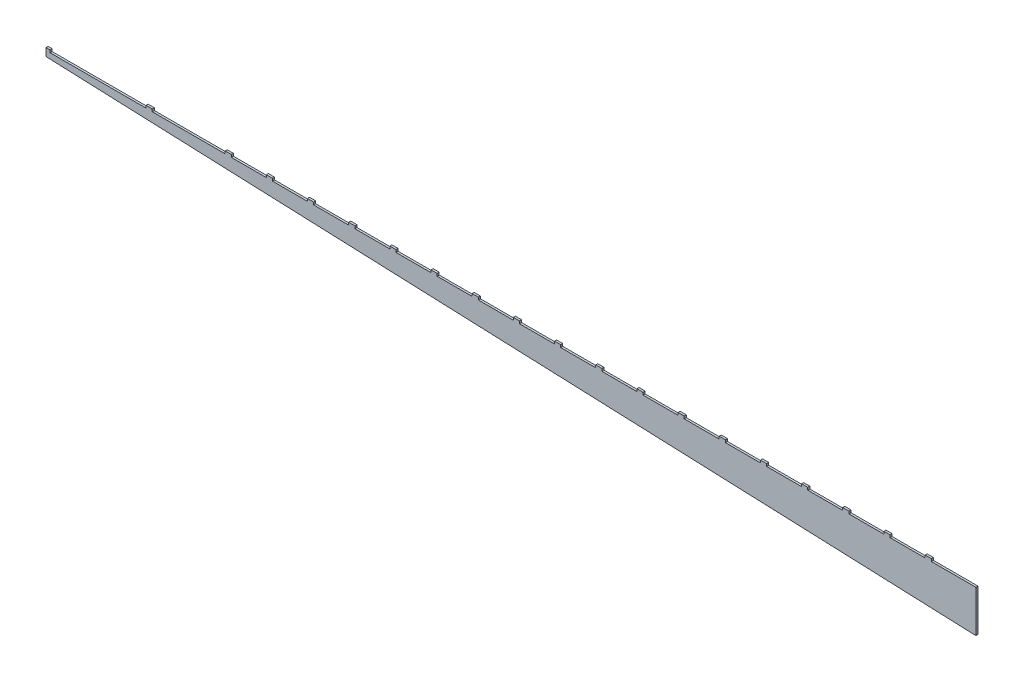
SolidWorks part; units mm, degrees
ref_plane "front" through (0, 0, 0) normal (0, 0, 1) x (1, 0, 0)
ref_plane "top" through (0, 0, 0) normal (0, 1, 0) x (1, 0, 0)
ref_plane "right" through (0, 0, 0) normal (1, 0, 0) x (0, 0, -1)
ref_axis "Axis1" through (-4.2838, 0, 0) along (1, 0, 0)
sketch "Sketch1" plane through (0, 0, 0) normal (0, 0, 1) x (1, 0, 0)
  line L0 (16.891, 0) -> (131.6228, 0)
  line L1 (131.6228, 0) -> (131.6228, -5.1715)
  line L2 (131.6228, -5.1715) -> (16.891, -0.6636)
  line L3 (16.891, -0.6636) -> (16.891, 0)
  line L4 (0, 0) -> (16.891, -1.4778) construction
  line L5 (0, 0) -> (16.891, -2.9783) construction
  circle A0 centre (130.0988, -1.397) radius 0.5969 construction
  circle A1 centre (130.0988, -3.683) radius 0.5969 construction
  point P11 (128.4732, 0)
  dimension "D6" = 1.1938
  dimension "D8" = 1.397
  dimension "D10" = 2.286
  dimension "D1" = 5
  dimension "D2" = 2.25
  dimension "D3" = 16.891
  dimension "D4" = 114.7318
  dimension "D5" = 128.4732
  dimension "D7" = 10
  dimension "D9" = 1.524
  dimension "D11" = 3.1496
  dimension "D12" = 1.6256
extrude "Extrude1" add sketch "Sketch1" along normal mid plane 0.254
sketch "Sketch4" plane through (0, 0, 0) normal (0, 0, 1) x (1, 0, 0)
  line L0 (16.891, 0) -> (16.891, 0.3048)
  line L1 (29.2354, 0.3048) -> (29.9974, 0.3048)
  line L2 (29.2354, 0.3048) -> (29.2354, -0.2032)
  line L3 (29.2354, -0.2032) -> (29.9974, -0.2032)
  line L4 (29.9974, 0.3048) -> (29.9974, -0.2032)
  line L5 (16.891, 0.3048) -> (17.399, 0.3048)
  line L6 (17.399, 0.3048) -> (17.399, 0)
  line L7 (16.891, 0) -> (131.6228, 0) construction
  line L8 (17.399, 0) -> (16.891, 0)
  line L9 (16.891, -0.6636) -> (16.891, 0) construction
  point P14 (29.6164, 0.3048)
  dimension "D1" = 0.3048
  dimension "D2" = 0.762
  dimension "D3" = 29.6164
  dimension "D4" = 0.508
  dimension "D5" = 0.3048
  dimension "D6" = 0.508
extrude "EB-02 Tab 1" add sketch "Sketch4" along normal mid plane 0.254
sketch "Sketch2" plane through (0, 0, 0) normal (0, 0, 1) x (1, 0, 0)
  line L1 (38.989, 0.3048) -> (39.751, 0.3048)
  line L2 (38.989, 0.3048) -> (38.989, -0.254)
  line L3 (38.989, -0.254) -> (39.751, -0.254)
  line L4 (39.751, 0.3048) -> (39.751, -0.254)
  point P4 (39.37, 0.3048)
  dimension "D1" = 0.3048
  dimension "D2" = 0.254
  dimension "D3" = 22.098
  dimension "D4" = 0.762
  dimension "D5" = 39.37
extrude "EB-02 Tab 2" add sketch "Sketch2" along normal mid plane 0.254
pattern_linear "LP-01 Tab 2 x 18" count 18 spacing 5.08 along (1, 0, 0) of "EB-02 Tab 2"
sketch "Sketch3" plane through (0, 0, 0) normal (0, 0, 1) x (1, 0, 0)
  line L0 (33.1898, 0.9632) -> (32.6719, -1.9744)
  line L1 (33.1898, 0.9632) -> (14.723, 0.9632)
  line L2 (14.723, 0.9632) -> (14.723, -1.9744)
  line L3 (14.723, -1.9744) -> (32.6719, -1.9744)
  line L5 (0, 0) -> (16.891, -2.9783) construction
  point P3 (33.02, 0)
  dimension "D1" = 33.02
  dimension "D2" = 0.9632
extrude "Extrude2" [suppressed] cut sketch "Sketch3" against normal mid plane 2.54
sketch "Sketch5" plane through (0, 0, 0.127) normal (0, 0, 1) x (1, 0, 0)
  line L0 (131.6228, -5.1715) -> (131.6228, 0) construction
  line L1 (16.891, -0.6636) -> (131.6228, -5.1715) construction
  line L2 (131.6228, -2.122) -> (131.6228, 0)
  line L3 (52.3757, -2.0578) -> (128.5757, -5.0518)
  arc A0 (129.2917, -5.6576) -> (132.2001, -2.8613) centre (131.6228, -5.1715) ccw
  arc A1 (132.2001, -2.8613) -> (131.6228, -2.122) centre (132.3848, -2.122) cw
  arc A2 (129.2917, -5.6576) -> (128.5757, -5.0518) centre (128.5457, -5.8132) ccw
  dimension "D1" = 4.7625
  dimension "D2" = 0.762
  dimension "D3" = 0.762
  dimension "D4" = 76.2
sketch "Sketch6" [suppressed] plane through (0, 0, -0.127) normal (0, 0, -1) x (-1, 0, 0)
  line L0 (-128.4478, 0) -> (-128.4478, -5.0467)
  line L1 (-131.6228, -2.122) -> (-131.6228, 0) construction
  line L2 (-52.3757, -2.0578) -> (-128.5757, -5.0518) construction
  line L3 (-131.6228, 0) -> (-126.111, 0) construction
  dimension "D1" = 3.175
sketch "Sketch7" [suppressed] plane through (0, 0, -0.127) normal (0, 0, -1) x (-1, 0, 0)
  line L0 (-32.7928, -1.2884) -> (-131.6228, -5.1715) construction
  line L1 (-131.6228, 0) -> (-128.7018, 0)
  line L2 (-131.6228, 0) -> (-131.6228, -5.1715)
  line L3 (-131.6228, -5.1715) -> (-128.7018, -5.0567)
  line L4 (-128.7018, 0) -> (-128.7018, -5.0567)
  line L5 (-131.6228, 0) -> (-126.111, 0) construction
  line L6 (-128.4478, 0) -> (-128.4478, -5.0467) construction
  dimension "D1" = 0.254
